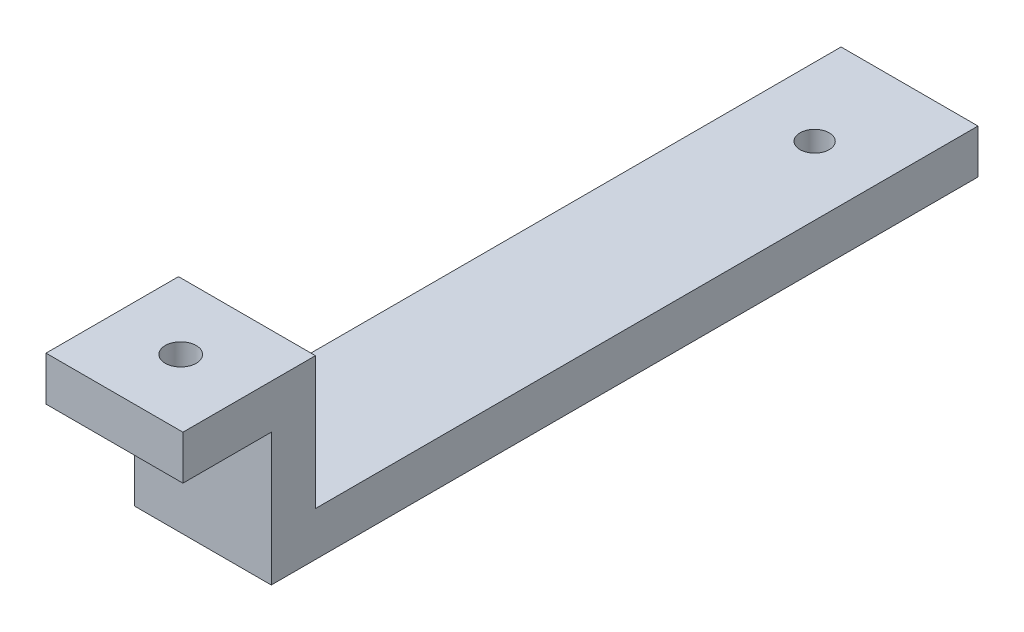
SolidWorks part; units mm, degrees
material "Galvanized Steel"
ref_plane "Front Plane" through (0, 0, 0) normal (0, 0, 1) x (1, 0, 0)
ref_plane "Top Plane" through (0, 0, 0) normal (0, 1, 0) x (1, 0, 0)
ref_plane "Right Plane" through (0, 0, 0) normal (1, 0, 0) x (0, 0, -1)
sketch "Sketch1" plane through (0, 0, 0) normal (1, 0, 0) x (0, 0, -1)
  line L0 (0, 0) -> (30, 0)
  line L1 (30, 0) -> (30, -29.972)
  line L2 (30, -29.972) -> (180, -29.972)
  dimension "D1" = 30
  dimension "D2" = 29.972
extrude "Extrude-Thin1" add sketch "Sketch1" along normal blind 31 thin contours L0 L1 L2 thin type one direction wall 10
sketch "Sketch6" plane through (0, 0, 0) normal (0, 1, 0) x (1, 0, 0)
  line L0 (0, 0) -> (0, 30) construction
  line L2 (31, 30) -> (0, 30) construction
  circle A0 centre (15.5, 15) radius 3.5
  dimension "D1" = 7
  dimension "D2" = 15.5
  dimension "D3" = 15
extrude "Cut-Extrude1" cut sketch "Sketch6" against normal blind 10
sketch "Sketch7" plane through (0, -29.972, 0) normal (0, 1, 0) x (1, 0, 0)
  line L0 (31, 30) -> (0, 30) construction
  line L2 (0, 30) -> (0, 180) construction
  circle A0 centre (15.494, 158.524) radius 3.302
  dimension "D1" = 6.604
  dimension "D3" = 15.494
  dimension "D2" = 128.524
extrude "Cut-Extrude3" cut sketch "Sketch7" against normal blind 10.16
